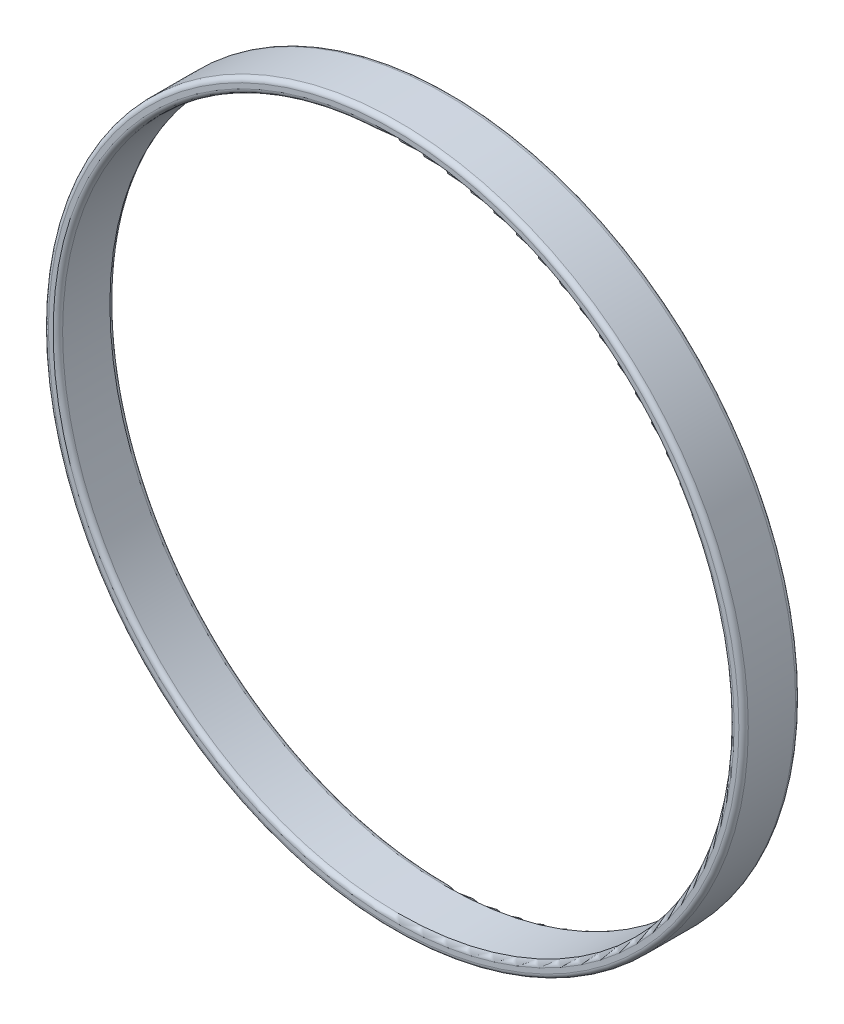
SolidWorks part; units mm, degrees
ref_plane "Front Plane" through (0, 0, 0) normal (0, 0, 1) x (1, 0, 0)
ref_plane "Top Plane" through (0, 0, 0) normal (0, 1, 0) x (1, 0, 0)
ref_plane "Right Plane" through (0, 0, 0) normal (1, 0, 0) x (0, 0, -1)
sketch "Sketch2" plane through (0, 0, 0) normal (0, 0, 1) x (1, 0, 0)
  circle A0 centre (0, 0) radius 35.5
  circle A1 centre (0, 0) radius 37
  dimension "D1" = 71
  dimension "D2" = 1.5
extrude "Boss-Extrude1" add sketch "Sketch2" along normal blind 6
fillet "Fillet1" radius 0.5 4 edges at (35.5, 0, 0) (37, 0, 0) (35.5, 0, 6) (37, 0, 6)
